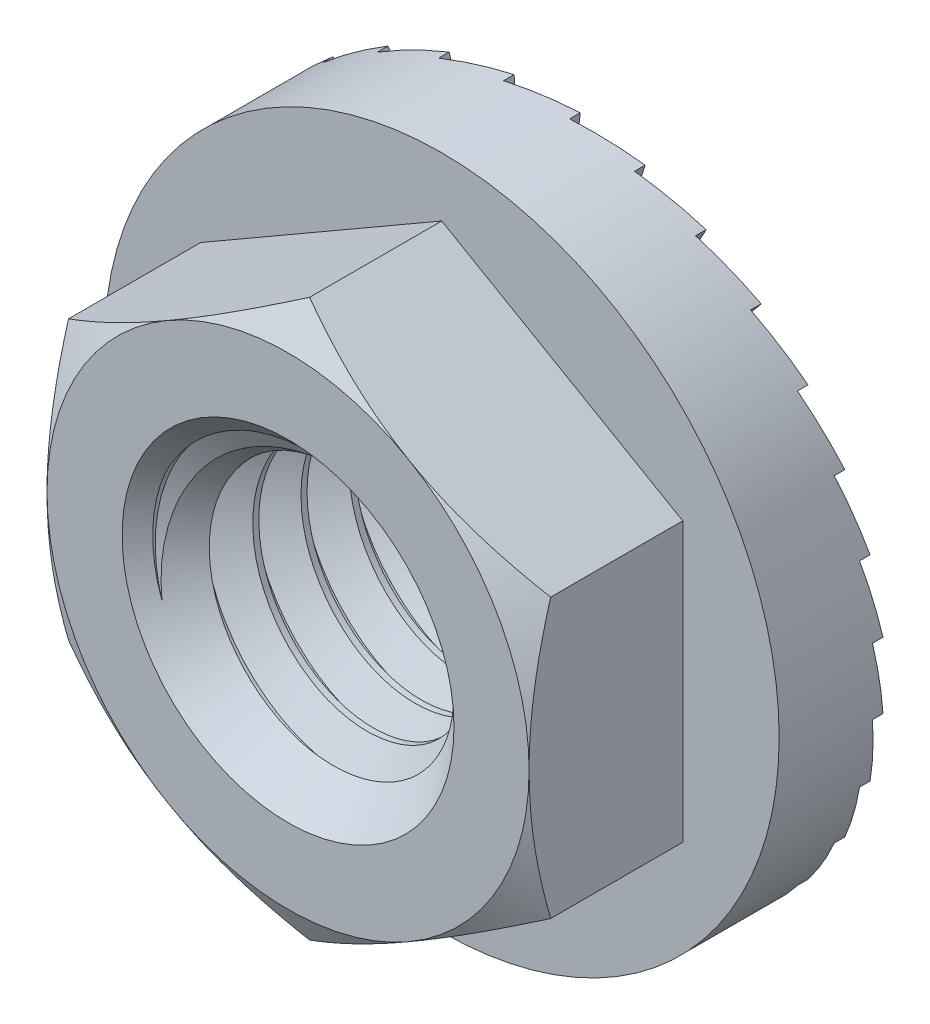
SolidWorks part; units mm, degrees
ref_plane "Front Plane" through (0, 0, 0) normal (0, 0, 1) x (1, 0, 0)
ref_plane "Top Plane" through (0, 0, 0) normal (0, 1, 0) x (1, 0, 0)
ref_plane "Right Plane" through (0, 0, 0) normal (1, 0, 0) x (0, 0, -1)
sketch "Sketch1" plane through (0, 0, 0) normal (0, 0, 1) x (1, 0, 0)
  line L1 (0, 4.6188) -> (-4, 2.3094)
  line L2 (-4, 2.3094) -> (-4, -2.3094)
  line L3 (-4, -2.3094) -> (0, -4.6188)
  line L4 (0, -4.6188) -> (4, -2.3094)
  line L5 (4, -2.3094) -> (4, 2.3094)
  line L6 (4, 2.3094) -> (0, 4.6188)
  circle A0 centre (0, 0) radius 4 construction
  dimension "Hex" = 8
extrude "Extrude1" add sketch "Sketch1" against normal blind 4.3
sketch "Sketch13" plane through (0, 0, -4.3) normal (0, 0, -1) x (-1, 0, 0)
  circle A0 centre (0, 0) radius 5.6
  dimension "Flange od" = 11.2
extrude "Extrude3" add sketch "Sketch13" against normal blind 1.75
sketch "Sketch2" plane through (0, 0, 0) normal (0, 0, 1) x (1, 0, 0)
  circle A0 centre (0, 0) radius 4 construction
  circle A1 centre (0, 0) radius 4
extrude "Cut-Extrude1" cut sketch "Sketch2" against normal through all draft 60 flip side to cut
sketch "Sketch4" plane through (0, 0, 0) normal (0, 0, 1) x (1, 0, 0)
  circle A0 centre (0, 0) radius 2.5
  dimension "Thread Dia" = 5
extrude "Cut-Extrude3" cut sketch "Sketch4" against normal through all
sketch "Sketch7" plane through (0, 0, 0) normal (0, 0, 1) x (1, 0, 0)
  circle A4 centre (0, 0) radius 2.754
  circle A5 centre (0, 0) radius 2.754
  dimension "D1" = 0.254
sketch "Sketch8" plane through (0, 0, -4.3) normal (0, 0, -1) x (-1, 0, 0)
  circle A1 centre (0, 0) radius 2.754
  circle A2 centre (0, 0) radius 2.754 construction
sketch "Sketch5" plane through (0, 0, 0) normal (0, 0, 1) x (1, 0, 0)
  circle A0 centre (0, 0) radius 2.5 construction
  circle A1 centre (0, 0) radius 2.5
curve "Helix/Spiral1" pitch 0.8 height 5.1 turns 6.375 parameters "pitch"=0.8
sketch "Sketch9" plane through (0, 0, 0) normal (1, 0, 0) x (0, 0, -1)
  line L0 (-0.4, 2.5) -> (-0.3, 2.5)
  line L1 (-0.3, 2.5) -> (0, 1.9804)
  line L2 (-0.4, 2.5) -> (-0.7, 1.9804)
  line L3 (-0.7, 1.9804) -> (0, 1.9804)
  line L4 (-0.35, 2.5) -> (-0.35, 1.9804) construction
  line L5 (-0.55, 2.2402) -> (-0.15, 2.2402) construction
  line L7 (0, 1.9804) -> (0, 2.5) construction
  line L8 (0, 2.5) -> (0, -2.5) construction
  dimension "D1" = 0.1
  dimension "D2" = 0.4
  dimension "D3" = 60
sketch "Sketch12" plane through (0, 0, 0) normal (0, 0, 1) x (1, 0, 0)
  circle A0 centre (0, 0) radius 1.9804
  circle A1 centre (0, 0) radius 2.5 construction
  circle A2 centre (0, 0) radius 2.5
extrude "Extrude2" add sketch "Sketch12" against normal up to surface (4.3 mm away)
sweep "Cut-Sweep1" cut profiles "Sketch9" path "Helix/Spiral1"
extrude "Cut-Extrude6" cut sketch "Sketch7" against normal through all draft 45
extrude "Cut-Extrude7" cut sketch "Sketch8" against normal through all draft 45
sketch "Sketch14" plane through (0, 0, -4.3) normal (0, 0, -1) x (-1, 0, 0)
  circle A4 centre (0, 0) radius 4.004
  circle A5 centre (0, 0) radius 4.004
  dimension "D1" = 1.25
extrude "Cut-Extrude8" cut sketch "Sketch14" against normal blind 0.175 flip side to cut
sketch "Sketch15" plane through (0, 0, -4.125) normal (0, 0, -1) x (-1, 0, 0)
  line L0 (-0.3925, 3.9847) -> (-0.5489, 5.573)
  line L1 (0.3925, 3.9847) -> (0.5489, 5.573)
  line L2 (0, 0) -> (0.3925, 3.9847) construction
  line L3 (0, 0) -> (-0.3925, 3.9847) construction
  circle A0 centre (0, 0) radius 5.6 construction
  circle A1 centre (0, 0) radius 4.004 construction
  arc A2 (0.5489, 5.573) -> (-0.5489, 5.573) centre (0, 0) ccw
  arc A3 (0.3925, 3.9847) -> (-0.3925, 3.9847) centre (0, 0) ccw
  dimension "D1" = 11.25
extrude "Extrude4" add sketch "Sketch15" along normal up to surface (0.175 mm away) separate body up to face at (-2.754, 0, -4.3)
sketch "Sketch16" plane through (0, 0, 0) normal (0, 1, 0) x (1, 0, 0)
  line L0 (-0.5489, 4.125) -> (0.5489, 4.3)
  line L4 (-0.5489, 4.125) -> (0.5489, 4.125)
  line L5 (0.5489, 4.125) -> (0.5489, 4.3)
  line L6 (0.5489, 4.3) -> (-0.5489, 4.3)
  line L7 (-0.5489, 4.3) -> (-0.5489, 4.125)
  line L8 (-0.5489, 4.125) -> (0.5489, 4.125) construction
  line L9 (0.5489, 4.125) -> (0.5489, 4.3) construction
  line L10 (0.5489, 4.3) -> (-0.5489, 4.3)
  line L11 (-0.5489, 4.3) -> (-0.5489, 4.125)
  dimension "D1" = 0
extrude "Cut-Extrude9" cut sketch "Sketch16" along normal through all
pattern_circular "CirPattern1" count 32 over 360 about axis through (0, 0, 0) along (0, 0, 1) of bodies 119
combine bodies "Combine1" operation type add bodies to combine 117 119 120 121 122 123 124 125 126 127 128 129 130 131 132 133 134 135 136 137 139 140 141 142 143 144 145 146 147 148 149 150 151
sketch "Sketch17" plane through (0, 0, 0) normal (1, 0, 0) x (0, 0, -1)
  line L0 (4.3, 5.6) -> (4.3, -5.6) construction
  line L1 (2.55, 5.6) -> (2.55, -5.6) construction
  dimension "D1" = 1.75
sketch "Sketch18" plane through (0, 0, -2.55) normal (0, 0, 1) x (1, 0, 0)
  circle A0 centre (0, 0) radius 5.6
  circle A1 centre (0, 0) radius 5.6 construction
equation "\"D2@Sketch9\" = \"pitch@Helix/Spiral1\"*.5"
equation "\"D3@Helix/Spiral1\" = \"pitch@Helix/Spiral1\"+\"Height@Extrude1\""
equation "\"D1@Sketch9\" = \"pitch@Helix/Spiral1\"*.125"
equation "\"D1@Cut-Extrude8\" = \"flange thickness@Extrude3\"*.1"
equation "\"D1@Sketch17\" = \"flange thickness@Extrude3\""
